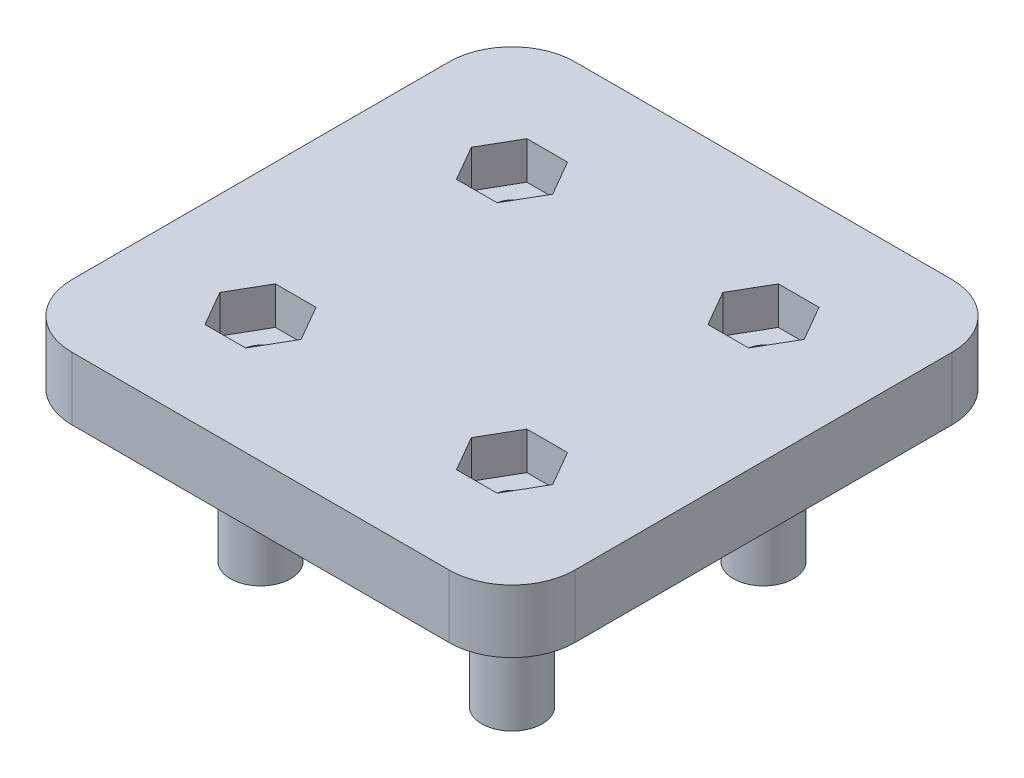
SolidWorks part; units mm, degrees
ref_plane "Front Plane" through (0, 0, 0) normal (0, 0, 1) x (1, 0, 0)
ref_plane "Top Plane" through (0, 0, 0) normal (0, 1, 0) x (1, 0, 0)
ref_plane "Right Plane" through (0, 0, 0) normal (1, 0, 0) x (0, 0, -1)
sketch "Sketch1" plane through (0, 0, 0) normal (0, 1, 0) x (1, 0, 0)
  line L1 (-20, -20) -> (20, -20)
  line L2 (-20, -20) -> (-20, 20)
  line L3 (-20, 20) -> (20, 20)
  line L4 (20, -20) -> (20, 20)
  line L5 (0, 20) -> (0, -20) construction
  line L6 (-20, 0) -> (20, 0) construction
  point P0 (0, 0)
  dimension "D1" = 40
  dimension "D2" = 40
extrude "Boss-Extrude1" add sketch "Sketch1" along normal blind 5
sketch "Sketch2" plane through (0, 5, 0) normal (0, 1, 0) x (1, 0, 0)
  line L1 (-10, -10) -> (10, -10)
  line L2 (-10, -10) -> (-10, 10)
  line L3 (-10, 10) -> (10, 10)
  line L4 (10, -10) -> (10, 10)
  line L5 (0, 10) -> (0, -10) construction
  line L6 (-10, 0) -> (10, 0) construction
  line L7 (-6.7668, 10) -> (-8.3834, 12.8)
  line L8 (-8.3834, 12.8) -> (-11.6166, 12.8)
  line L9 (-11.6166, 12.8) -> (-13.2332, 10)
  line L10 (-13.2332, 10) -> (-11.6166, 7.2)
  line L11 (-11.6166, 7.2) -> (-8.3834, 7.2)
  line L12 (-8.3834, 7.2) -> (-6.7668, 10)
  line L13 (13.2332, 10) -> (11.6166, 12.8)
  line L14 (11.6166, 12.8) -> (8.3834, 12.8)
  line L15 (8.3834, 12.8) -> (6.7668, 10)
  line L16 (6.7668, 10) -> (8.3834, 7.2)
  line L17 (8.3834, 7.2) -> (11.6166, 7.2)
  line L18 (11.6166, 7.2) -> (13.2332, 10)
  line L19 (-6.7668, -10) -> (-8.3834, -7.2)
  line L20 (-8.3834, -7.2) -> (-11.6166, -7.2)
  line L21 (-11.6166, -7.2) -> (-13.2332, -10)
  line L22 (-13.2332, -10) -> (-11.6166, -12.8)
  line L23 (-11.6166, -12.8) -> (-8.3834, -12.8)
  line L24 (-8.3834, -12.8) -> (-6.7668, -10)
  line L25 (13.2332, -10) -> (11.6166, -7.2)
  line L26 (11.6166, -7.2) -> (8.3834, -7.2)
  line L27 (8.3834, -7.2) -> (6.7668, -10)
  line L28 (6.7668, -10) -> (8.3834, -12.8)
  line L29 (8.3834, -12.8) -> (11.6166, -12.8)
  line L30 (11.6166, -12.8) -> (13.2332, -10)
  circle A4 centre (-10, 10) radius 2.8 construction
  circle A5 centre (10, 10) radius 2.8 construction
  circle A6 centre (-10, -10) radius 2.8 construction
  circle A7 centre (10, -10) radius 2.8 construction
  point P0 (0, 0)
  dimension "D3" = 5.6
  dimension "D1" = 20
  dimension "D2" = 20
extrude "Cut-Extrude1" cut sketch "Sketch2" against normal blind 3 contours L3 L2 | L2 L3 | L4 L3 | L3 L4 | L2 L1 | L1 L2 | L1 L4 | L4 L1 region at (-8.7427, 5, 8.7556) region at (-10.4191, 5, 10.4148) region at (8.7427, 5, 8.7556) region at (10.4191, 5, 10.4148) region at (-10.4191, 5, -10.4148) region at (-8.7427, 5, -8.7556) region at (8.7427, 5, -8.7556) region at (10.4191, 5, -10.4148)
sketch "Sketch3" plane through (0, 2, 0) normal (0, 1, 0) x (1, 0, 0)
  circle A0 centre (-10, 10) radius 1.4
  circle A1 centre (10, 10) radius 1.4
  circle A2 centre (-10, -10) radius 1.4
  circle A3 centre (10, -10) radius 1.4
  circle A4 centre (-10, 10) radius 2.4
  circle A5 centre (-10, -10) radius 2.4
  circle A6 centre (10, -10) radius 2.4
  circle A7 centre (10, 10) radius 2.4
  dimension "D1" = 2.8
  dimension "D2" = 4.8
extrude "Cut-Extrude2" cut sketch "Sketch3" against normal through all contours A0 | A3 | A1 | A2 region at (-10, 2, -10) region at (10, 2, -10) region at (10, 2, 10)
fillet "Fillet1" radius 5 4 edges at (-20, 2.5, 20) (20, 2.5, 20) (20, 2.5, -20) (-20, 2.5, -20)
extrude "Boss-Extrude2" add sketch "Sketch3<3>" against normal blind 13.9
sketch "Sketch3<3>" plane through (0, 2, 0) normal (0, 1, 0) x (1, 0, 0) same geometry as "Sketch3"
